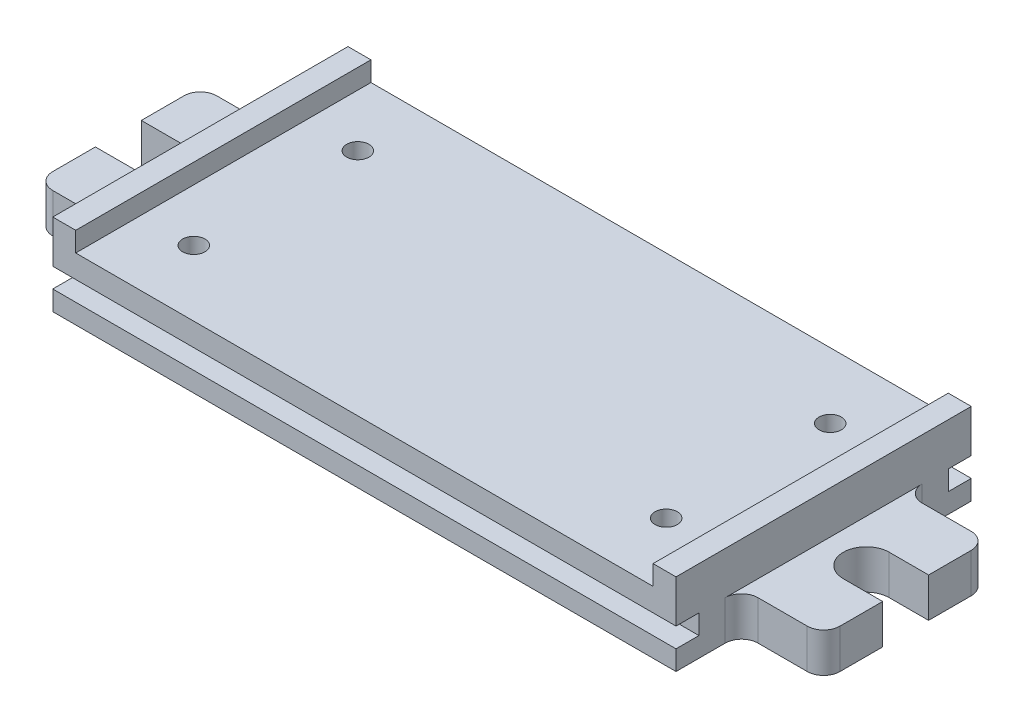
SolidWorks part; units mm, degrees
ref_plane "Front Plane" through (0, 0, 0) normal (0, 0, 1) x (1, 0, 0)
ref_plane "Top Plane" through (0, 0, 0) normal (0, 1, 0) x (1, 0, 0)
ref_plane "Right Plane" through (0, 0, 0) normal (1, 0, 0) x (0, 0, -1)
sketch "Sketch1" plane through (0, 0, 0) normal (0, 1, 0) x (1, 0, 0)
  line L0 (-95, 25) -> (-115, 25)
  line L1 (-95, -45) -> (95, -45)
  line L2 (-95, -45) -> (-95, 45)
  line L3 (-95, 45) -> (95, 45)
  line L4 (95, -45) -> (95, 45)
  line L5 (-95, -45) -> (95, 45) construction
  line L6 (-95, 45) -> (95, -45) construction
  line L7 (-120, 20) -> (-120, 7)
  line L8 (-120, 7) -> (-108, 7)
  line L9 (-108, -7) -> (-120, -7)
  line L10 (-120, -7) -> (-120, -20)
  line L11 (-115, -25) -> (-95, -25)
  line L12 (0, 0) -> (0, -36.4055) construction
  line L13 (115, -25) -> (95, -25)
  line L14 (120, -7) -> (120, -20)
  line L15 (108, -7) -> (120, -7)
  line L16 (120, 7) -> (108, 7)
  line L17 (120, 20) -> (120, 7)
  line L18 (95, 25) -> (115, 25)
  line L19 (-88, 45) -> (-88, -45)
  line L20 (88, 45) -> (88, -45)
  line L22 (-77, -30) -> (77, -30)
  line L23 (-82, -25) -> (-82, 25)
  line L24 (-77, 30) -> (77, 30)
  line L25 (82, -25) -> (82, 25)
  line L26 (-82, -30) -> (82, 30) construction
  line L27 (-82, 30) -> (82, -30) construction
  arc A0 (-115, 25) -> (-120, 20) centre (-115, 20) ccw
  arc A1 (-108, 7) -> (-108, -7) centre (-108, 0) cw
  arc A2 (-120, -20) -> (-115, -25) centre (-115, -20) ccw
  arc A3 (120, -20) -> (115, -25) centre (115, -20) cw
  arc A4 (108, 7) -> (108, -7) centre (108, 0) ccw
  arc A5 (115, 25) -> (120, 20) centre (115, 20) cw
  arc A6 (77, -30) -> (82, -25) centre (77, -25) ccw
  arc A7 (77, 30) -> (82, 25) centre (77, 25) cw
  arc A8 (-77, -30) -> (-82, -25) centre (-77, -25) cw
  arc A9 (-82, 25) -> (-77, 30) centre (-77, 25) cw
  point P0 (0, 0)
  dimension "D7" = 5
  dimension "D8" = 19
  dimension "D13" = 5
  dimension "D1" = 190
  dimension "D2" = 90
  dimension "D3" = 14
  dimension "D4" = 20
  dimension "D5" = 20
  dimension "D6" = 25
  dimension "D9" = 7
  dimension "D10" = 7
  dimension "D11" = 164
  dimension "D12" = 60
extrude "Boss-Extrude2" add sketch "Sketch1" along normal blind 25 contours L19 L3 L2 L1 | L3 L20 L1 L4 region at (-91.5, 0, 0) region at (91.5, 0, 0)
extrude "Boss-Extrude3" add sketch "Sketch1<4>" along normal blind 19 contours L20 L3 L19 L1 L23 A9 L24 A7 L25 A6 L22 A8 | A9 L23 A8 L22 A6 L25 A7 L24 region at (0, 0, -43.0232) region at (0, 0, 0)
sketch "Sketch1<4>" plane through (0, 0, 0) normal (0, 1, 0) x (1, 0, 0) same geometry as "Sketch1"
extrude "Boss-Extrude4" add sketch "Sketch1<5>" along normal blind 12 contours A5 L18 L4 L13 A3 L14 L15 A4 L16 L17 | L10 A2 L11 L2 L0 A0 L7 L8 A1 L9 region at (-95.559, 0, 0) region at (105, 0, -24.441)
sketch "Sketch1<5>" plane through (0, 0, 0) normal (0, 1, 0) x (1, 0, 0) same geometry as "Sketch1"
fillet "Fillet2" radius 5 4 edges at (95, 6, 25) (95, 6, -25) (-95, 6, -25) (-95, 6, 25)
extrude "Cut-Extrude3" cut sketch "Sketch1<6>" along normal blind 6 contours A9 L23 A8 L22 A6 L25 A7 L24 region at (0, 0, 0)
sketch "Sketch1<6>" plane through (0, 0, 0) normal (0, 1, 0) x (1, 0, 0) same geometry as "Sketch1"
sketch "Sketch7" plane through (-95, 0, 0) normal (-1, 0, 0) x (0, 0, 1)
  line L0 (0, 0) -> (0, 50000) construction
  line L1 (-7, 0) -> (7, 0) construction
  line L2 (45, 25) -> (45, 0) construction
  line L3 (45, 12) -> (38, 12)
  line L4 (45, 12) -> (45, 6)
  line L5 (45, 6) -> (38, 6)
  line L6 (38, 12) -> (38, 6)
  line L7 (-45, 6) -> (-38, 6)
  line L8 (-38, 12) -> (-38, 6)
  line L9 (-45, 12) -> (-38, 12)
  line L10 (-45, 12) -> (-45, 6)
  line L11 (45, 0) -> (30, 0) construction
  point P4 (0, 0)
  dimension "D1" = 6
  dimension "D2" = 6
  dimension "D3" = 7
extrude "Cut-Extrude4" cut sketch "Sketch7" against normal through all both and the other way through all
hole_wizard "M8 Tapped Hole1" positions "Sketch9" profile "Sketch10" tap size "M8" standard "ISO" end condition through all
sketch "Sketch9" plane through (0, 19, 0) normal (0, 1, 0) x (1, 0, 0)
  line L0 (-100, 25) -> (-115, 25) construction
  line L1 (-88, 45) -> (-88, -45) construction
  line L2 (0, 0) -> (0, 45) construction
  line L3 (-88, 45) -> (88, 45) construction
  line L5 (-115, -25) -> (-100, -25) construction
  point P0 (-72, 25)
  point P2 (72, 25)
  point P4 (72, -25)
  point P6 (-72, -25)
  point P22 (0, 0)
  point P23 (0, 0)
  dimension "D1" = 16
sketch "Sketch10" plane through (-72, 19, -25) normal (1, 0, 0) x (0, 0, 1)
  line L0 (0, 0) -> (0, 19)
  line L1 (0, 19) -> (3.4, 19)
  line L2 (3.4, 19) -> (3.4, 0)
  line L5 (3.4, 0) -> (0, 0)
  line L11 (0, -6.35) -> (0, 107.95) construction
  dimension "Thru Tap Drill Dia." = 6.8
  dimension "Thru Tap Drill Depth" = 19
cosmetic thread "Hole Thread1" parameters "D2"=8
cosmetic thread "Hole Thread2" parameters "D2"=8
cosmetic thread "Hole Thread3" parameters "D2"=8
cosmetic thread "Hole Thread4" parameters "D2"=8
